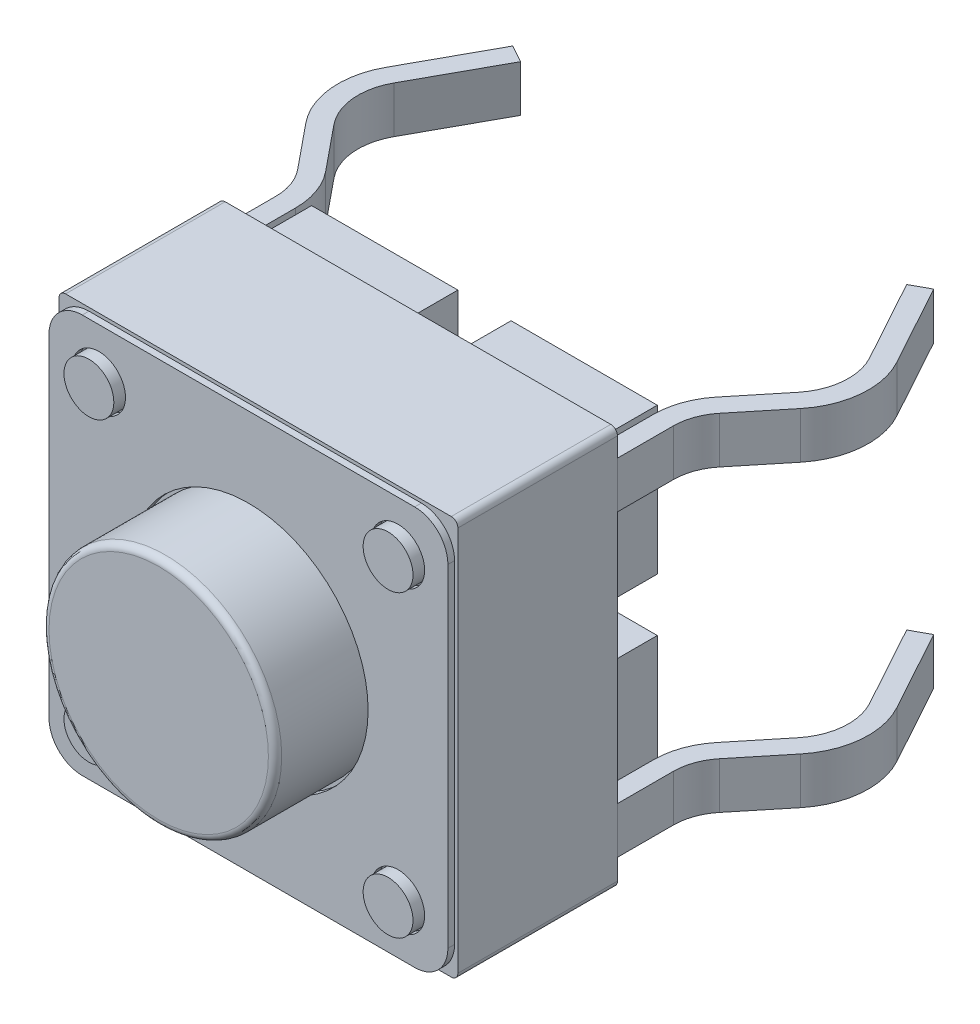
SolidWorks part; units mm, degrees
ref_plane "Front" through (0, 0, 0) normal (0, 0, 1) x (1, 0, 0)
ref_plane "Top" through (0, 0, 0) normal (0, 1, 0) x (1, 0, 0)
ref_plane "Right" through (0, 0, 0) normal (1, 0, 0) x (0, 0, -1)
sketch "Эскиз1" plane through (0, 0, 0) normal (0, 0, 1) x (1, 0, 0)
  line L1 (0, 0) -> (6, 0)
  line L2 (0, 0) -> (0, 6)
  line L3 (0, 6) -> (6, 6)
  line L4 (6, 0) -> (6, 6)
  dimension "D1" = 6
extrude "Бобышка-Вытянуть1" add sketch "Эскиз1" along normal blind 3.4
sketch "Эскиз2" plane through (0, 0, 0) normal (0, 0, -1) x (-1, 0, 0)
  line L0 (-3, 6) -> (-3, 0) construction
  line L1 (-6, 6) -> (0, 6)
  line L2 (-6, 6) -> (-6, 0)
  line L3 (-6, 0) -> (0, 0)
  line L4 (0, 6) -> (0, 0)
  line L5 (-6, 3) -> (0, 3) construction
  line L6 (-3, 6) -> (-6, 3) construction
  line L7 (-6, 6) -> (-3, 3) construction
  line L8 (-2.6, 5.6) -> (-0.4, 5.6)
  line L9 (-5.6, 5.6) -> (-3.4, 5.6)
  line L10 (-5.6, 5.6) -> (-5.6, 3.4)
  line L11 (-5.6, 3.4) -> (-3.4, 3.4)
  line L12 (-3.4, 5.6) -> (-3.4, 3.4)
  line L13 (-5.6, 5.6) -> (-3.4, 3.4) construction
  line L14 (-5.6, 3.4) -> (-3.4, 5.6) construction
  line L15 (-2.6, 5.6) -> (-2.6, 3.4)
  line L16 (-2.6, 3.4) -> (-0.4, 3.4)
  line L17 (-0.4, 5.6) -> (-0.4, 3.4)
  line L18 (-2.6, 2.6) -> (-0.4, 2.6)
  line L19 (-2.6, 2.6) -> (-2.6, 0.4)
  line L20 (-2.6, 0.4) -> (-0.4, 0.4)
  line L21 (-0.4, 2.6) -> (-0.4, 0.4)
  line L22 (-5.6, 2.6) -> (-3.4, 2.6)
  line L23 (-5.6, 2.6) -> (-5.6, 0.4)
  line L24 (-5.6, 0.4) -> (-3.4, 0.4)
  line L25 (-3.4, 2.6) -> (-3.4, 0.4)
  point P10 (-3, 3)
  point P11 (-4.5, 4.5)
  dimension "D1" = 0.4
  dimension "D2" = 2
  dimension "D3" = 2
extrude "Вырез-Вытянуть1" cut sketch "Эскиз2" against normal blind 1
sketch "Эскиз3" plane through (0, 0, 3.4) normal (0, 0, 1) x (1, 0, 0)
  line L0 (3, 6) -> (3, 0) construction
  line L1 (0.5, 0) -> (5.5, 0)
  line L2 (0, 0.5) -> (0, 5.5)
  line L3 (0.5, 6) -> (5.5, 6)
  line L4 (6, 0.5) -> (6, 5.5)
  line L5 (0, 3) -> (6, 3) construction
  line L6 (0, 0) -> (6, 0) construction
  line L7 (6, 0) -> (6, 6) construction
  arc A0 (0.5, 0) -> (0, 0.5) centre (0.5, 0.5) cw
  arc A1 (5.5, 0) -> (6, 0.5) centre (5.5, 0.5) ccw
  arc A2 (5.5, 6) -> (6, 5.5) centre (5.5, 5.5) cw
  arc A3 (0, 5.5) -> (0.5, 6) centre (0.5, 5.5) cw
  circle A4 centre (0.75, 5.25) radius 0.4
  circle A5 centre (5.25, 5.25) radius 0.4
  circle A6 centre (5.25, 0.75) radius 0.4
  circle A7 centre (0.75, 0.75) radius 0.4
  circle A8 centre (3, 3) radius 1.8
  point P8 (0, 0)
  point P13 (6, 6)
  dimension "D1" = 0.5
  dimension "D2" = 0.8
  dimension "D5" = 3.6
  dimension "D3" = 4.5
  dimension "D4" = 4.5
extrude "Бобышка-Вытянуть2" add sketch "Эскиз3" along normal blind 0.1 from offset 0.05 separate body
sketch "Эскиз4" plane through (0, 0, 3.4) normal (0, 0, 1) x (1, 0, 0)
  line L0 (3, 6) -> (3, 0) construction
  line L1 (5.5, 6) -> (0.5, 6) construction
  line L2 (0.5, 0) -> (5.5, 0) construction
  line L3 (0, 3) -> (6, 3) construction
  line L4 (0, 5.5) -> (0, 0.5) construction
  line L5 (6, 0.5) -> (6, 5.5) construction
  circle A0 centre (3, 3) radius 1.75
  circle A1 centre (0.75, 5.25) radius 0.375
  circle A2 centre (5.25, 5.25) radius 0.375
  circle A3 centre (5.25, 0.75) radius 0.375
  circle A4 centre (0.75, 0.75) radius 0.375
  dimension "D1" = 3.5
  dimension "D2" = 0.75
extrude "Бобышка-Вытянуть3" add sketch "Эскиз4" along normal blind 1.5 contours A0 region at (3, 3, 3.4)
extrude "Бобышка-Вытянуть4" add sketch "Эскиз4<3>" along normal blind 0.3 contours A1 | A2 | A4 | A3 region at (0.75, 5.25, 3.4) region at (5.25, 5.25, 3.4) region at (5.25, 0.75, 3.4) region at (0.75, 0.75, 3.4)
sketch "Эскиз4<3>" plane through (0, 0, 3.4) normal (0, 0, 1) x (1, 0, 0) same geometry as "Эскиз4"
sketch "Эскиз5" plane through (0, 0, 0) normal (0, -1, 0) x (1, 0, 0)
  line L0 (0.2, 1) -> (0.2, 0.1503)
  line L1 (6, 1) -> (0, 1) construction
  line L2 (-0.0249, -0.4816) -> (-0.5742, -1.1554)
  line L3 (-0.6759, -2.2684) -> (0, -3.5)
  line L4 (0, 1) -> (0, -4.2279) construction
  line L5 (2.6, 0) -> (0.4, 0) construction
  line L6 (0, 1) -> (6, 1) construction
  line L7 (0, 3.4) -> (0, 1) construction
  arc A0 (0.2, 0.1503) -> (-0.0249, -0.4816) centre (-0.8, 0.1503) cw
  arc A1 (-0.5742, -1.1554) -> (-0.6759, -2.2684) centre (0.2008, -1.7873) ccw
  point P12 (3, 1)
  point P21 (-1, -1.6777)
  dimension "D4" = 1
  dimension "D1" = 3.5
  dimension "D2" = 4
  dimension "D3" = 0.2
sketch "Эскиз7" plane through (0, 0, 1) normal (0, 0, -1) x (-1, 0, 0)
  line L0 (0, 0) -> (0, 6) construction
  line L1 (-0.01, 0.4) -> (-0.31, 0.4)
  line L2 (-0.01, 0.4) -> (-0.01, 1.1)
  line L3 (-0.01, 1.1) -> (-0.31, 1.1)
  line L4 (-0.31, 0.4) -> (-0.31, 1.1)
  line L5 (0, 3) -> (-2.1721, 3) construction
  line L6 (-0.01, 0.75) -> (-1.3406, 0.75) construction
  line L7 (-0.01, 5.6) -> (-0.01, 4.9)
  line L8 (-0.01, 5.6) -> (-0.31, 5.6)
  line L9 (-0.31, 5.6) -> (-0.31, 4.9)
  line L10 (-0.01, 4.9) -> (-0.31, 4.9)
  dimension "D1" = 0.3
  dimension "D2" = 0.7
  dimension "D3" = 2.25
  dimension "D4" = 0.01
sweep "По траектории1" add profiles "Эскиз7" path "Эскиз5"
ref_plane "Плоскость1" through (3, 0, 0) normal (-1, 0, 0) x (0, 0, 1)
mirror "Зеркальное отражение1" about plane through (3, 0, 0) normal (-1, 0, 0) of "По траектории1"
fillet "Скругление1" radius 0.1 5 edges at (4.75, 3, 4.9) (6, 6, 2.2) (6, 0, 2.2) (0, 0, 2.2) (0, 6, 2.2)
